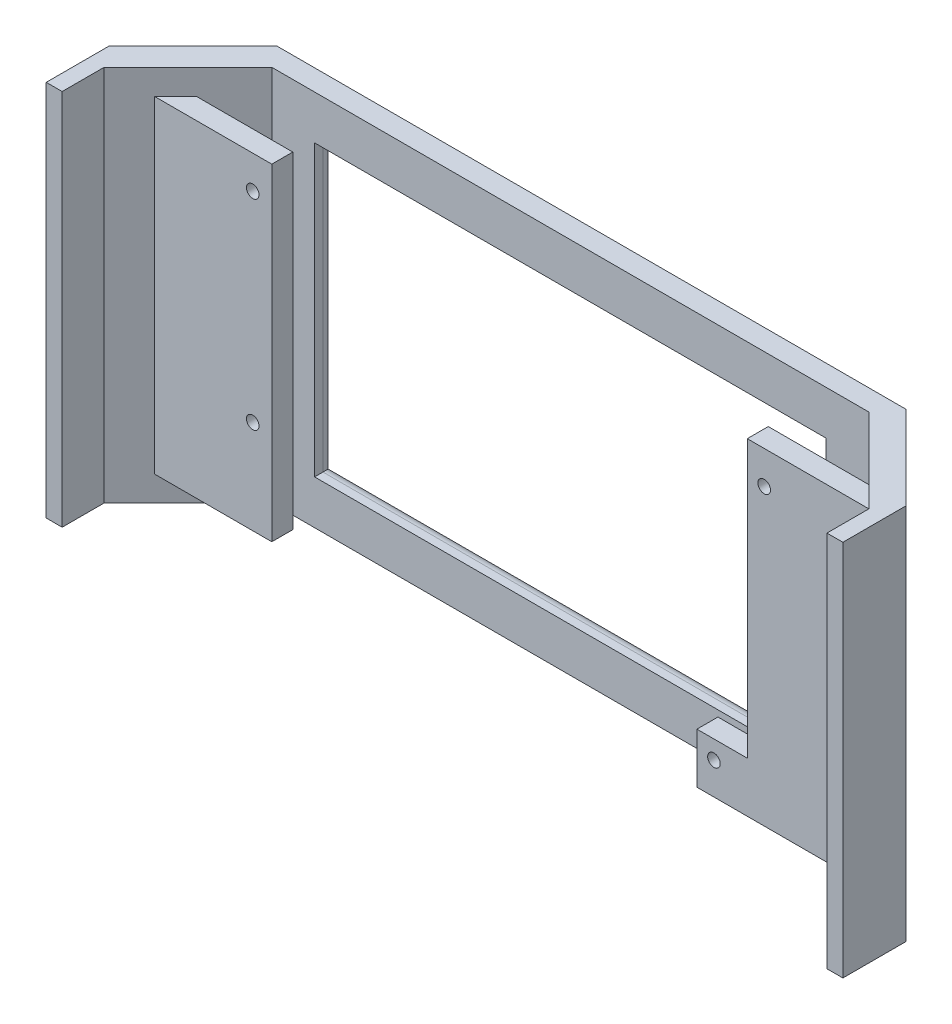
SolidWorks part; units mm, degrees
ref_plane "Front Plane" through (0, 0, 0) normal (0, 0, 1) x (1, 0, 0)
ref_plane "Top Plane" through (0, 0, 0) normal (0, 1, 0) x (1, 0, 0)
ref_plane "Right Plane" through (0, 0, 0) normal (1, 0, 0) x (0, 0, -1)
sketch "Sketch1" plane through (0, 0, 0) normal (0, 0, 1) x (1, 0, 0)
  line L1 (-95, 45) -> (95, 45)
  line L2 (-95, 45) -> (-95, -45)
  line L3 (-95, -45) -> (95, -45)
  line L4 (95, 45) -> (95, -45)
  line L5 (-95, 45) -> (95, -45) construction
  line L6 (-95, -45) -> (95, 45) construction
  line L7 (-61, 34.5) -> (61, 34.5)
  line L8 (-61, 34.5) -> (-61, -34.5)
  line L9 (-61, -34.5) -> (61, -34.5)
  line L10 (61, 34.5) -> (61, -34.5)
  line L11 (-61, 34.5) -> (61, -34.5) construction
  line L12 (-61, -34.5) -> (61, 34.5) construction
  point P0 (0, 0)
  point P6 (0, 0)
  dimension "D1" = 122
  dimension "D2" = 190
  dimension "D3" = 69
  dimension "D4" = 90
extrude "Boss-Extrude1" add sketch "Sketch1" along normal blind 5
sketch "Sketch2" plane through (0, 0, 5) normal (0, 0, 1) x (1, 0, 0)
  line L0 (-95, -45) -> (95, -45) construction
  line L1 (-95, 45) -> (-91.2, 45)
  line L2 (-95, 45) -> (-95, -45)
  line L3 (-95, -45) -> (-91.2, -45)
  line L4 (-91.2, 45) -> (-91.2, -45)
  line L5 (0, 0) -> (0, 45) construction
  line L6 (95, 45) -> (-95, 45) construction
  line L7 (95, -45) -> (91.2, -45)
  line L8 (91.2, 45) -> (91.2, -45)
  line L9 (95, 45) -> (91.2, 45)
  line L10 (95, 45) -> (95, -45)
  dimension "D1" = 3.8
extrude "Boss-Extrude2" add sketch "Sketch2" along normal blind 30
sketch "Sketch3" plane through (0, 45, 0) normal (0, 1, 0) x (1, 0, 0)
  line L0 (-91.2, -35) -> (-91.2, -5) construction
  line L1 (-91.2, -14) -> (-57.2, -14)
  line L2 (-91.2, -14) -> (-91.2, -19)
  line L3 (-91.2, -19) -> (-57.2, -19)
  line L4 (-57.2, -14) -> (-57.2, -19)
  line L5 (91.2, -35) -> (91.2, -5) construction
  line L6 (91.2, -14) -> (44.2, -14)
  line L7 (91.2, -14) -> (91.2, -19)
  line L8 (91.2, -19) -> (44.2, -19)
  line L9 (44.2, -14) -> (44.2, -19)
  line L10 (91.2, -5) -> (-91.2, -5) construction
  dimension "D1" = 9
  dimension "D2" = 9
  dimension "D3" = 5
  dimension "D4" = 5
  dimension "D5" = 34
  dimension "D6" = 47
extrude "Boss-Extrude3" add sketch "Sketch3" against normal up to surface (90 mm away) up to face at (0, -45, 18.75)
sketch "Sketch4" plane through (0, 0, 19) normal (0, 0, 1) x (1, 0, 0)
  line L0 (91.2, -45) -> (91.2, 45) construction
  line L1 (-91.2, 45) -> (91.2, 45)
  line L2 (-91.2, 45) -> (-91.2, 39)
  line L3 (-91.2, 39) -> (91.2, 39)
  line L4 (91.2, 45) -> (91.2, 39)
  line L5 (0, 0) -> (-91.2, 0) construction
  line L6 (-91.2, -45) -> (-91.2, 45) construction
  line L7 (-91.2, -39) -> (91.2, -39)
  line L8 (91.2, -45) -> (91.2, -39)
  line L9 (-91.2, -45) -> (91.2, -45)
  line L10 (-91.2, -45) -> (-91.2, -39)
  dimension "D1" = 6
extrude "Cut-Extrude1" cut sketch "Sketch4" against normal blind 5
sketch "Sketch5" plane through (0, 0, 19) normal (0, 0, 1) x (1, 0, 0)
  line L0 (0, 0) -> (-61.75, 0) construction
  line L1 (-70.2, 37.38) -> (70.2, 37.38) construction
  line L2 (-70.2, 37.38) -> (-70.2, -37.38) construction
  line L3 (-70.2, -37.38) -> (70.2, -37.38) construction
  line L4 (70.2, 37.38) -> (70.2, -37.38) construction
  line L5 (-70.2, 37.38) -> (70.2, -37.38) construction
  line L6 (-70.2, -37.38) -> (70.2, 37.38) construction
  line L7 (-61.75, 0) -> (-61.75, 31.13) construction
  line L8 (-61.75, 0) -> (-61.75, -16.61) construction
  line L9 (48.25, 0) -> (60.23, 0) construction
  line L10 (60.23, 0) -> (60.23, 31.13) construction
  line L11 (0, 0) -> (48.25, 0) construction
  line L12 (48.25, 0) -> (48.25, -31.38) construction
  circle A0 centre (-61.75, 31.13) radius 1.5
  circle A1 centre (-61.75, -16.61) radius 1.5
  circle A2 centre (60.23, 31.13) radius 1.5
  circle A3 centre (48.25, -31.38) radius 1.5
  point P0 (0, 0)
  dimension "D10" = 3
  dimension "D11" = 3
  dimension "D12" = 3
  dimension "D13" = 3
  dimension "D1" = 140.4
  dimension "D2" = 74.76
  dimension "D3" = 61.75
  dimension "D4" = 31.13
  dimension "D5" = 16.61
  dimension "D6" = 60.23
  dimension "D7" = 31.13
  dimension "D8" = 48.25
  dimension "D9" = 31.38
extrude "Cut-Extrude2" cut sketch "Sketch5" against normal up to surface (5 mm away) up to face at (67.7, 0, 14)
sketch "Sketch6" plane through (0, 0, 19) normal (0, 0, 1) x (1, 0, 0)
  line L1 (44.2, 39) -> (56.2, 39)
  line L2 (44.2, 39) -> (44.2, -27)
  line L3 (44.2, -27) -> (56.2, -27)
  line L4 (56.2, 39) -> (56.2, -27)
  dimension "D1" = 12
  dimension "D2" = 66
extrude "Cut-Extrude3" cut sketch "Sketch6" against normal up to surface (5 mm away) up to face at (46.75, -31.38, 14)
fillet "Fillet3" radius 3 4 edges at (-61, 0, 0) (0, -34.5, 0) (61, 0, 0) (0, 34.5, 0)
chamfer "Chamfer6" distance 20 angle 45 4 edges at (91.2, 0, 5) (95, 0, 0) (-95, 0, 0) (-91.2, 0, 5)
